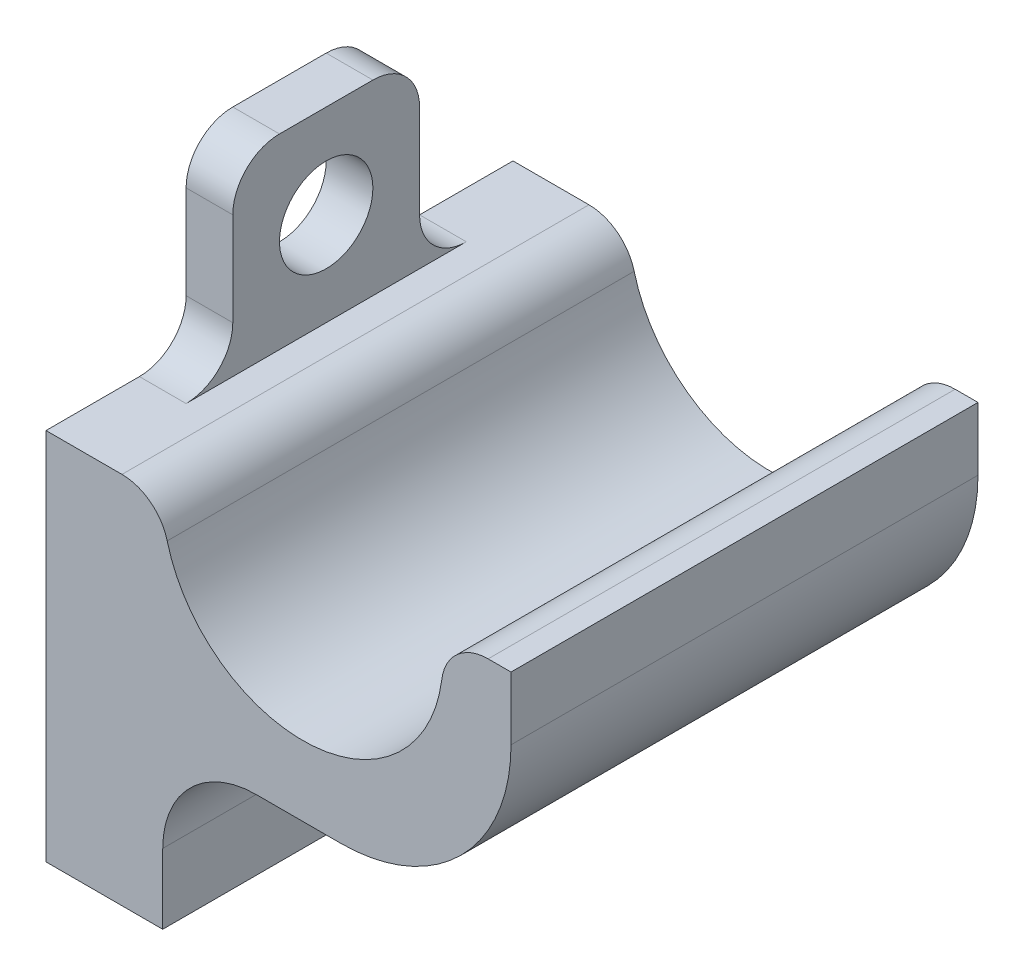
SolidWorks part; units mm, degrees
ref_plane "Alzado" through (0, 0, 0) normal (0, 0, 1) x (1, 0, 0)
ref_plane "Planta" through (0, 0, 0) normal (0, 1, 0) x (1, 0, 0)
ref_plane "Vista lateral" through (0, 0, 0) normal (1, 0, 0) x (0, 0, -1)
sketch "Croquis1" plane through (0, 0, 0) normal (0, 0, 1) x (1, 0, 0)
sketch_block_instance "seguro-2"
sketch_block "seguro" parameters "D1"=6, "D2"=7, "D3"=16, "D4"=5, "D5"=10, "D6"=3
sketch "Croquis2" plane through (0, 0, 0) normal (0, 0, 1) x (1, 0, 0)
  line L0 (23.961, 4.3104) -> (23.961, 20.3104) construction
  line L1 (23.961, 4.3104) -> (28.961, 4.3104) construction
  line L2 (28.961, 4.3104) -> (28.961, 11.3104) construction
  line L3 (28.961, 11.3104) -> (43.8771, 11.3104) construction
  line L4 (43.8771, 11.3104) -> (43.8771, 21.3104) construction
  line L5 (40.8771, 21.3104) -> (43.8771, 21.3104) construction
  line L6 (23.961, 20.3104) -> (28.961, 20.3104) construction
  line L7 (23.961, 4.3104) -> (23.961, 20.3104)
  line L8 (23.961, 4.3104) -> (28.961, 4.3104)
  line L9 (28.961, 4.3104) -> (28.961, 11.3104)
  line L10 (28.961, 11.3104) -> (43.8771, 11.3104)
  line L11 (43.8771, 11.3104) -> (43.8771, 21.3104)
  line L12 (40.8771, 21.3104) -> (43.8771, 21.3104)
  line L13 (23.961, 20.3104) -> (28.961, 20.3104)
  arc A0 (28.961, 20.3104) -> (40.8771, 21.3104) centre (34.961, 20.3104) ccw construction
  arc A1 (28.961, 20.3104) -> (40.8771, 21.3104) centre (34.961, 20.3104) ccw
extrude "Saliente-Extruir1" add sketch "Croquis2" along normal blind 10 and the other way blind 10
sketch "Croquis3" plane through (0, 0, 0) normal (0, 0, 1) x (1, 0, 0)
  line L0 (28.961, 11.3104) -> (43.8771, 11.3104) construction
  line L1 (28.961, 4.3104) -> (28.961, 11.3104) construction
  line L2 (28.961, 11.3104) -> (43.8771, 11.3104) construction
  line L3 (28.961, 4.3104) -> (28.961, 11.3104)
  line L4 (36.419, 11.3104) -> (28.961, 4.3104)
  line L5 (36.419, 11.3104) -> (28.961, 11.3104)
extrude "Saliente-Extruir2" add sketch "Croquis3" along normal blind 2 and the other way blind 2
fillet "Redondeo1" radius 4 2 edges at (28.961, 11.3104, -6) (28.961, 11.3104, 6)
fillet "Redondeo4" radius 7.3 1 edges at (43.8771, 11.3104, 0)
fillet "Redondeo2" radius 2 2 edges at (28.961, 20.3104, 0) (40.8771, 21.3104, 0)
sketch "Croquis4" plane through (0, 20.3104, 0) normal (0, 1, 0) x (1, 0, 0)
  line L0 (23.961, 4) -> (23.961, -4)
  line L1 (23.961, 10) -> (23.961, -10) construction
  line L2 (23.961, -4) -> (25.961, -4)
  line L3 (25.961, -4) -> (25.961, 4)
  line L4 (25.961, 4) -> (23.961, 4)
  point P5 (23.961, 0)
  dimension "D1" = 8
  dimension "D2" = 2
extrude "Saliente-Extruir3" add sketch "Croquis4" along normal blind 8
fillet "Redondeo3" radius 2 4 edges at (24.961, 28.3104, 4) (24.961, 28.3104, -4) (24.961, 20.3104, -4) (24.961, 20.3104, 4)
sketch "Croquis5" plane through (25.961, 0, 0) normal (1, 0, 0) x (0, 0, -1)
  line L0 (0, 28.3104) -> (0, 20.3104) construction
  line L1 (-2, 28.3104) -> (2, 28.3104) construction
  line L2 (-6, 20.3104) -> (6, 20.3104) construction
  circle A0 centre (0, 24.3104) radius 2
  dimension "D1" = 4
extrude "Cortar-Extruir1" cut sketch "Croquis5" against normal up to next
